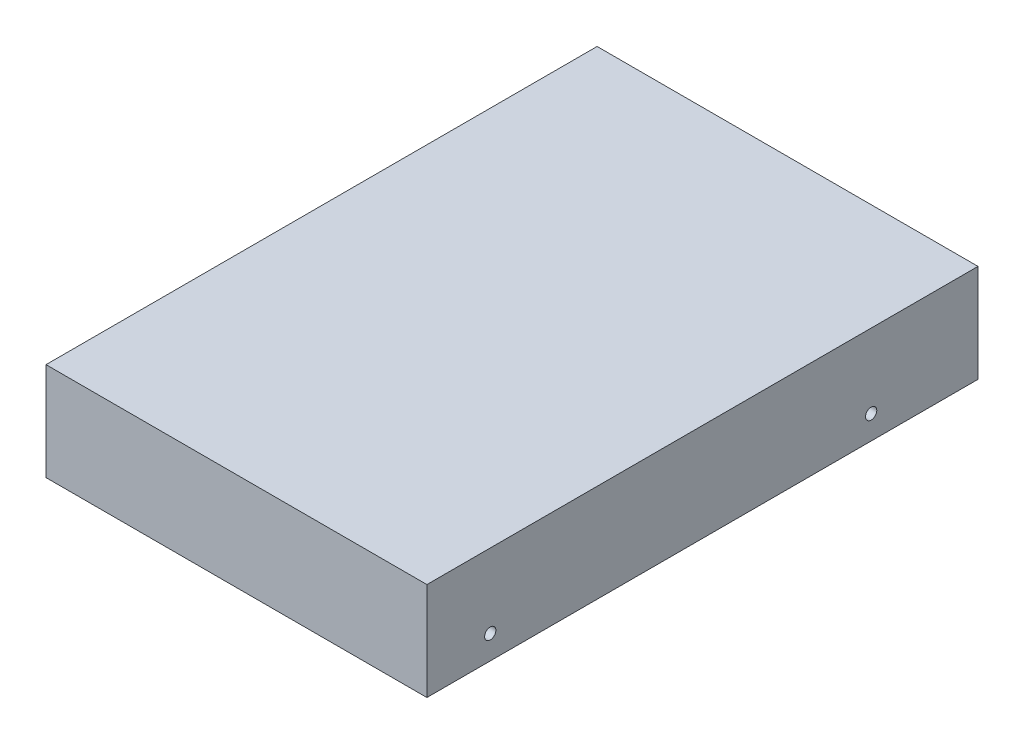
SolidWorks part; units mm, degrees
ref_plane "Front Plane" through (0, 0, 0) normal (0, 0, 1) x (1, 0, 0)
ref_plane "Top Plane" through (0, 0, 0) normal (0, 1, 0) x (1, 0, 0)
ref_plane "Right Plane" through (0, 0, 0) normal (1, 0, 0) x (0, 0, -1)
sketch "Sketch1" plane through (0, 0, 0) normal (0, 1, 0) x (1, 0, 0)
  line L1 (0, 0) -> (101.6, 0)
  line L2 (0, 0) -> (0, 147)
  line L3 (0, 147) -> (101.6, 147)
  line L4 (101.6, 0) -> (101.6, 147)
extrude "Boss-Extrude1" add sketch "Sketch1" along normal blind 26.1
sketch "Sketch2" plane through (0, 0, 0) normal (1, 0, 0) x (0, 0, -1)
  line L0 (147, 26.1) -> (147, 0) construction
  line L1 (55.88, 0) -> (-55.88, 0) construction
  circle A0 centre (16.9, 6.35) radius 1.7526
  circle A1 centre (118.5, 6.35) radius 1.7526
  dimension "D1" = 28.5
  dimension "D2" = 101.6
  dimension "D3" = 6.35
  dimension "D4" = 6.35
extrude "Boss-Extrude2" add sketch "Sketch2" along normal blind 3.175
extrude "Cut-Extrude2" cut sketch "Sketch2<2>" along normal blind 3
sketch "Sketch2<2>" plane through (0, 0, 0) normal (1, 0, 0) x (0, 0, -1) same geometry as "Sketch2"
ref_plane "Plane1" through (101.6, 0, 0) normal (1, 0, 0) x (0, 0, -1)
sketch "Sketch4" plane through (101.6, 0, 0) normal (1, 0, 0) x (0, 0, -1)
  line L0 (147, 26.1) -> (147, 0) construction
  line L1 (55.88, 0) -> (-55.88, 0) construction
  circle A0 centre (118.5, 6.35) radius 1.5
  circle A1 centre (16.9, 6.35) radius 1.5
  dimension "D1" = 28.5
  dimension "D3" = 101.6
  dimension "D2" = 6.35
extrude "Cut-Extrude3" cut sketch "Sketch4" against normal blind 3
